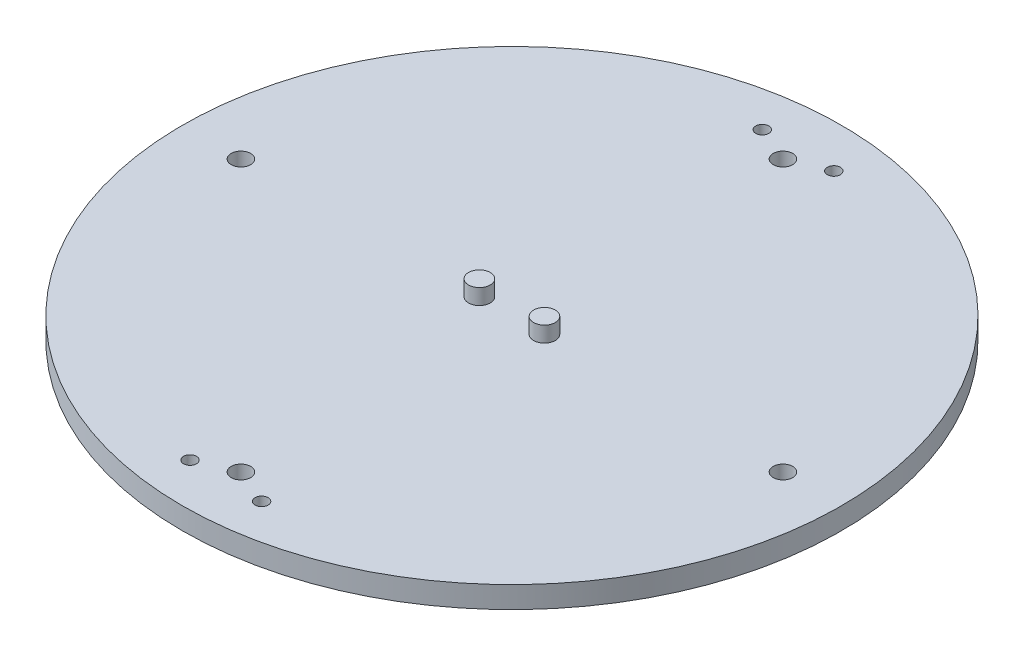
SolidWorks part; units mm, degrees
material "Aluminum Bronze"
ref_plane "Front Plane" through (0, 0, 0) normal (0, 0, 1) x (1, 0, 0)
ref_plane "Top Plane" through (0, 0, 0) normal (0, 1, 0) x (1, 0, 0)
ref_plane "Right Plane" through (0, 0, 0) normal (1, 0, 0) x (0, 0, -1)
sketch "Sketch1" plane through (0, 0, 0) normal (0, 1, 0) x (1, 0, 0)
  circle A0 centre (0, 0) radius 76
  circle A1 centre (0, 0) radius 62.5 construction
  circle A2 centre (62.5, 0) radius 2.25
  circle A3 centre (0, 62.5) radius 2.25
  circle A4 centre (-62.5, 0) radius 2.25
  circle A5 centre (0, -62.5) radius 2.25
  dimension "D1" = 4.5
  dimension "D2" = 152
  dimension "D3" = 125
extrude "Boss-Extrude1" add sketch "Sketch1" along normal blind 5 contours A0 | A4 | A4 | A3 | A3 | A2 | A2 | A5 | A5 region at (0, 0, 0) region at (62.5, 0, 0) region at (0, 0, -62.5) region at (-62.5, 0, 0) region at (0, 0, 62.5)
extrude "Cut-Extrude2" cut sketch "Sketch1<5>" along normal blind 5 contours A4 | A3 | A2 | A5 region at (62.5, 0, 0) region at (0, 0, -62.5) region at (-62.5, 0, 0)
sketch "Sketch1<5>" plane through (0, 0, 0) normal (0, 1, 0) x (1, 0, 0) same geometry as "Sketch1"
sketch "Sketch3" plane through (0, 0, 0) normal (0, -1, 0) x (1, 0, 0)
  line L0 (0, 0) -> (114.2389, 0) construction
  line L1 (0, 0) -> (0, 84.4662) construction
  line L7 (-10, -2.5) -> (10, -2.5)
  line L8 (-10, -2.5) -> (-10, 2.5)
  line L17 (-10, 2.5) -> (10, 2.5)
  line L18 (10, -2.5) -> (10, 2.5)
  line L19 (-10, -2.5) -> (10, 2.5) construction
  line L20 (-10, 2.5) -> (10, -2.5) construction
  point P1 (0, 0)
  point P2 (0, 0)
  dimension "D1" = 20
  dimension "D2" = 5
extrude "Boss-Extrude4" add sketch "Sketch3" along normal blind 20
sketch "Sketch6" plane through (0, 0, -2.5) normal (0, 0, -1) x (-1, 0, 0)
  line L0 (0, -20) -> (0, 0)
  line L1 (10, -20) -> (-10, -20) construction
  line L2 (10, 0) -> (-10, 0) construction
  line L3 (-5, -10) -> (-5, 0)
  line L4 (5, -10) -> (5, 0)
  circle A0 centre (0, -10) radius 5
  line M2 (10, 0) -> (-10, 0)
  dimension "D1" = 10
extrude "Cut-Extrude5" cut sketch "Sketch6" against normal blind 30 contours A0 L4 L0 M2 | A0 L0 L3 M2 | L0 A0 | A0 L0 region at (2.1221, -10, -2.5) region at (-2.1221, -10, -2.5) region at (2.7444, -3.139, -2.5) region at (-2.7444, -3.139, -2.5)
fillet "Fillet12" radius 10 2 edges at (-10, -20, 0) (10, -20, 0)
fillet "Fillet15" radius 2.5 14 edges at (-10, -5, 2.5) (-7.0711, -17.0711, 2.5) (7.0711, -17.0711, 2.5) (10, -5, 2.5) (-10, -5, -2.5) (-7.0711, -17.0711, -2.5) (7.0711, -17.0711, -2.5) (10, -5, -2.5) (5, -5, 2.5) (0, -15, 2.5) (5, -5, -2.5) (0, -15, -2.5) (-5, -5, 2.5) (-5, -5, -2.5)
sketch "Sketch7" plane through (0, 5, 0) normal (0, 1, 0) x (1, 0, 0)
  arc A0 (-5, 0) -> (-7.5, 2.5) centre (-7.5, 0) ccw construction
  arc A1 (-7.5, 2.5) -> (-10, 0) centre (-7.5, 0) ccw construction
  arc A2 (-10, 0) -> (-7.5, -2.5) centre (-7.5, 0) ccw construction
  arc A3 (-7.5, -2.5) -> (-5, 0) centre (-7.5, 0) ccw construction
  arc A4 (7.5, 2.5) -> (5, 0) centre (7.5, 0) ccw construction
  arc A5 (5, 0) -> (7.5, -2.5) centre (7.5, 0) ccw construction
  arc A6 (7.5, -2.5) -> (10, 0) centre (7.5, 0) ccw construction
  arc A7 (10, 0) -> (7.5, 2.5) centre (7.5, 0) ccw construction
  arc A8 (-5, 0) -> (-7.5, 2.5) centre (-7.5, 0) ccw
  arc A9 (-7.5, 2.5) -> (-10, 0) centre (-7.5, 0) ccw
  arc A10 (-10, 0) -> (-7.5, -2.5) centre (-7.5, 0) ccw
  arc A11 (-7.5, -2.5) -> (-5, 0) centre (-7.5, 0) ccw
  arc A12 (7.5, 2.5) -> (5, 0) centre (7.5, 0) ccw
  arc A13 (5, 0) -> (7.5, -2.5) centre (7.5, 0) ccw
  arc A14 (7.5, -2.5) -> (10, 0) centre (7.5, 0) ccw
  arc A15 (10, 0) -> (7.5, 2.5) centre (7.5, 0) ccw
extrude "Boss-Extrude5" add sketch "Sketch7" along normal blind 3.6
sketch "Sketch8" plane through (0, 8.6, 0) normal (0, 1, 0) x (1, 0, 0)
  circle A0 centre (7.5, 0) radius 2.5 construction
  circle A1 centre (7.5, 0) radius 2.5
sketch "Sketch9" plane through (0, 5, 0) normal (0, 1, 0) x (1, 0, 0)
  line L0 (2.25, 62.5) -> (-2.25, 62.5)
  line L1 (-2.25, 62.5) -> (-3.25, 62.5)
  line L2 (-3.25, 62.5) -> (-13.25, 62.5)
  line L3 (2.25, 62.5) -> (3.25, 62.5)
  line L4 (3.25, 62.5) -> (13.25, 62.5)
  line L5 (0, 62.5) -> (0, 65.9791)
  line L6 (0, 65.9791) -> (-8.25, 65.9791)
  line L7 (0, 0) -> (0, 9.6416) construction
  line L8 (0, 0) -> (19.0147, 0) construction
  circle A0 centre (0, 62.5) radius 2.25 construction
  circle A1 centre (0, 62.5) radius 2.25
  circle A2 centre (-8.25, 65.9791) radius 1.5
  circle A3 centre (8.25, 65.9791) radius 1.5
  circle A4 centre (8.25, -65.9791) radius 1.5
  circle A5 centre (-8.25, -65.9791) radius 1.5
  dimension "D7" = 3
  dimension "D1" = 1
  dimension "D2" = 10
  dimension "D3" = 1
  dimension "D4" = 10
  dimension "D5" = 3.4791
  dimension "D6" = 8.25
extrude "Cut-Extrude6" cut sketch "Sketch9" against normal blind 30 contours A5 | A4 | A2 | A3 region at (-9.7076, 5, -65.9791) region at (8.25, 5, -65.9791) region at (8.25, 5, 65.9791) region at (-8.25, 5, 65.9791)
